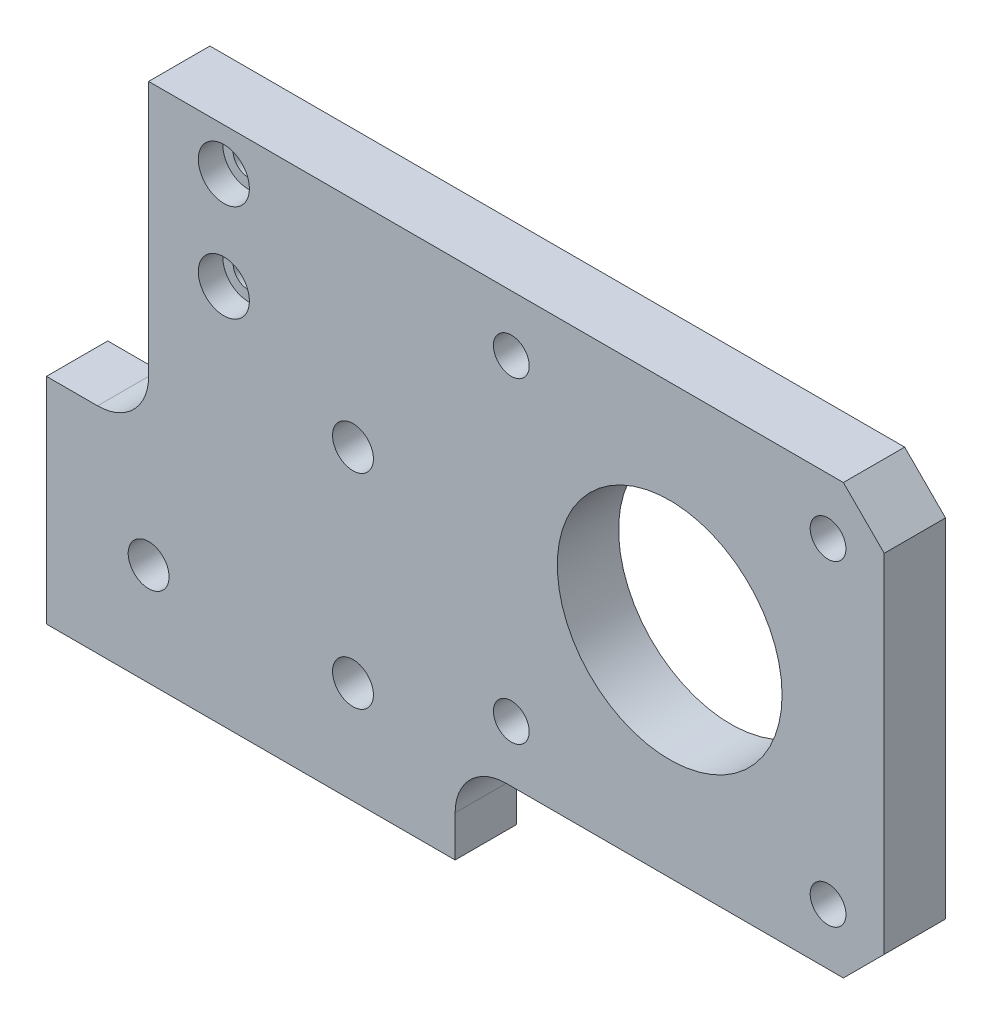
SolidWorks part; units mm, degrees
ref_plane "Plano frontal" through (0, 0, 0) normal (0, 0, 1) x (1, 0, 0)
ref_plane "Plano superior" through (0, 0, 0) normal (0, 1, 0) x (1, 0, 0)
ref_plane "Plano direito" through (0, 0, 0) normal (1, 0, 0) x (0, 0, -1)
sketch "Esboço1" plane through (0, 0, 0) normal (0, 0, 1) x (1, 0, 0)
  line L0 (30, 0) -> (30, 51) construction
  line L1 (0, 0) -> (40, 0)
  line L2 (0, 0) -> (0, 51)
  line L3 (0, 51) -> (40, 51)
  line L4 (40, 0) -> (40, 51)
  line L5 (40, 9) -> (82, 9)
  line L6 (40, 9) -> (40, 51)
  line L7 (40, 51) -> (82, 51)
  line L8 (82, 9) -> (82, 51)
  line L9 (45.5, 45.5) -> (76.5, 45.5) construction
  line L10 (45.5, 45.5) -> (45.5, 14.5) construction
  line L11 (45.5, 14.5) -> (76.5, 14.5) construction
  line L12 (76.5, 45.5) -> (76.5, 14.5) construction
  line L13 (45.5, 45.5) -> (76.5, 14.5) construction
  line L14 (45.5, 14.5) -> (76.5, 45.5) construction
  line L15 (0, 10) -> (40, 10) construction
  line L16 (10, 0) -> (10, 51) construction
  line L17 (0, 30) -> (40, 30) construction
  line L18 (61, 51) -> (61, 9) construction
  line L19 (82, 30) -> (61, 30) construction
  circle A0 centre (45.5, 45.5) radius 1.75
  circle A1 centre (76.5, 45.5) radius 1.75
  circle A2 centre (76.5, 14.5) radius 1.75
  circle A3 centre (45.5, 14.5) radius 1.75
  circle A4 centre (61, 30) radius 11
  circle A5 centre (30, 10) radius 2
  circle A6 centre (10, 10) radius 2
  circle A7 centre (30, 30) radius 2
  point P9 (82, 30)
  point P10 (61, 30)
  point P37 (0, 0)
  point P38 (61.5454, 30)
  dimension "D5" = 3.5
  dimension "D6" = 22
  dimension "D11" = 4
  dimension "D2" = 40
  dimension "D3" = 42
  dimension "D4" = 30
  dimension "D12" = 31
  dimension "D10" = 20
  dimension "D7" = 10
  dimension "D8" = 10
  dimension "D9" = 20
extrude "Ressalto-extrusão1" add sketch "Esboço1" along normal blind 6 contours L1 L4 L3 L2 A7 A6 A5 | L5 L8 L7 L6 L4 A4 A3 A2 A1 A0 region at (19.9372, 25.6663, 0) region at (40.594, 30, 0)
chamfer "Chanfro1" distance 4 angle 45 2 edges at (82, 9, 3) (82, 51, 3)
sketch "Esboço2" plane through (0, 0, 0) normal (0, 0, -1) x (-1, 0, 0)
  line L1 (0, 51) -> (-10, 51)
  line L2 (0, 51) -> (0, 21)
  line L3 (0, 21) -> (-10, 21)
  line L4 (-10, 51) -> (-10, 21)
  dimension "D1" = 30
  dimension "D2" = 10
extrude "Corte-extrusão1" cut sketch "Esboço2" against normal up to surface (6 mm away) up to face at (32, 30, 6)
fillet "Filete2" radius 5 2 edges at (40, 9, 3) (10, 21, 3)
sketch "Esboço5" plane through (0, 0, 0) normal (0, 0, -1) x (-1, 0, 0)
  circle A0 centre (-17.3625, 37.3125) radius 1.175 construction
  circle A1 centre (-17.3625, 46.8375) radius 1.175 construction
  circle A2 centre (-17.3625, 37.3125) radius 1.175 construction
  circle A3 centre (-17.3625, 46.8375) radius 1.175 construction
  circle A4 centre (-17.3625, 46.8375) radius 1.5
  circle A5 centre (-17.3625, 37.3125) radius 1.5
  dimension "D1" = 3
extrude "Corte-extrusão3" cut sketch "Esboço5" against normal up to surface (6 mm away) up to face at (39.1667, 21, 6)
sketch "Esboço6" plane through (0, 0, 6) normal (0, 0, 1) x (1, 0, 0)
  circle A0 centre (17.3625, 46.8375) radius 2.5
  circle A1 centre (17.3625, 37.3125) radius 2.5
  dimension "D1" = 5
extrude "Corte-extrusão4" cut sketch "Esboço6" against normal blind 2.4
